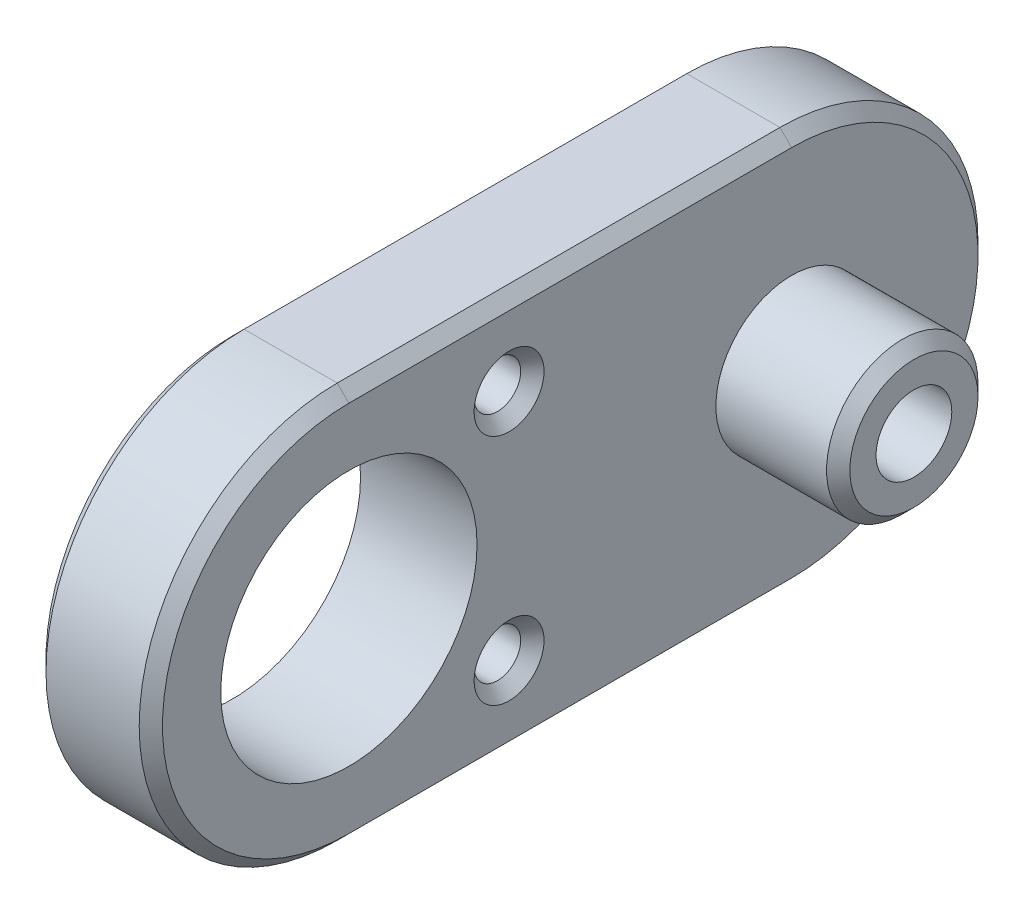
SolidWorks part; units mm, degrees
ref_plane "Front Plane" through (0, 0, 0) normal (0, 0, 1) x (1, 0, 0)
ref_plane "Top Plane" through (0, 0, 0) normal (0, 1, 0) x (1, 0, 0)
ref_plane "Right Plane" through (0, 0, 0) normal (1, 0, 0) x (0, 0, -1)
sketch "Sketch1" plane through (0, 0, 0) normal (1, 0, 0) x (0, 0, -1)
  line L0 (0, 0) -> (-19, 0) construction
  line L1 (0, -8.5) -> (-19, -8.5)
  line L2 (0, 8.5) -> (-19, 8.5)
  line L3 (-27.5, 0) -> (8.5, 0) construction
  line L4 (-14.5522, -3.2353) -> (-12.9348, -4.4118) construction
  arc A0 (0, -8.5) -> (0, 8.5) centre (0, 0) ccw
  arc A1 (-19, 8.5) -> (-19, -8.5) centre (-19, 0) ccw
  circle A2 centre (0, 0) radius 1.625
  circle A3 centre (-19, 0) radius 5.5
  circle A4 centre (-12.1261, -5) radius 1
  circle A6 centre (-12.1261, 5) radius 1
  circle A8 centre (0, 0) radius 3.25
  circle A9 centre (0, 0) radius 3.25
  point P3 (-9.5, 0)
  point P13 (-19, 5.5)
  point P22 (-12.9348, -4.4118)
  point P23 (-14.5522, -3.2353)
  dimension "D2" = 3.25
  dimension "D3" = 11
  dimension "D5" = 2
  dimension "D7" = 2
  dimension "D1" = 19
  dimension "D4" = 3
  dimension "D6" = 5
  dimension "D8" = 0.25
extrude "Boss-Extrude1" add sketch "Sketch1" along normal blind 5 contours A2 L1 A0 L2 | A2 | A9 region at (0, 0, 8.0461) region at (0, 0, 0)
extrude "Boss-Extrude2" add sketch "Sketch1<3>" along normal offset from surface (10.25 mm away) 0.25 contours A2 A9 region at (0, 0, 3.1581) offset beyond the face yes
sketch "Sketch1<3>" plane through (0, 0, 0) normal (1, 0, 0) x (0, 0, -1) same geometry as "Sketch1"
sketch "Sketch2" plane through (0, 0, 0) normal (-1, 0, 0) x (0, 0, 1)
  line L1 (0, 3.3198) -> (-2.875, 1.6599)
  line L2 (-2.875, 1.6599) -> (-2.875, -1.6599)
  line L3 (-2.875, -1.6599) -> (0, -3.3198)
  line L4 (0, -3.3198) -> (2.875, -1.6599)
  line L5 (2.875, -1.6599) -> (2.875, 1.6599)
  line L6 (2.875, 1.6599) -> (0, 3.3198)
  circle A0 centre (0, 0) radius 2.875 construction
  dimension "D1" = 5.75
extrude "Cut-Extrude1" cut sketch "Sketch2" against normal blind 3 contours L4 L5 L6 L1 L2 L3
chamfer "Chamfer2" distance 0.5 angle 45 19 edges at (0, 0, 27.5) (5, -5, 11.1261) (0, -5, 11.1261) (0, 0, -8.5) (0, 8.5, 9.5) (0, -8.5, 9.5) (5, -8.5, 9.5) (5, 0, -8.5) (5, 0, 27.5) (5, 8.5, 9.5) (0, 2.4898, 1.4375) (0, 2.4898, -1.4375) (0, 0, -2.875) (0, -2.4898, -1.4375) (0, -2.4898, 1.4375) (0, 0, 2.875) (5, 5, 11.1261) (0, 5, 11.1261) (10.25, 0, -3.25)
